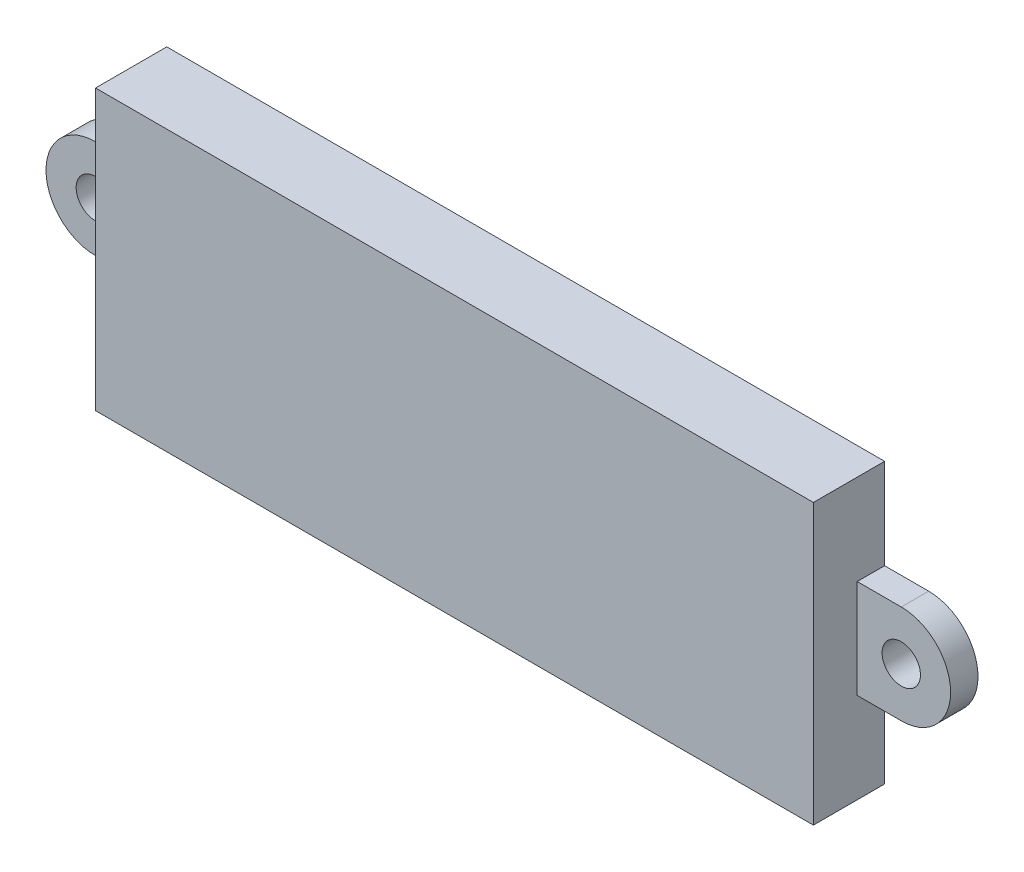
SolidWorks part; units mm, degrees
ref_plane "Спереди" through (0, 0, 0) normal (0, 0, 1) x (1, 0, 0)
ref_plane "Сверху" through (0, 0, 0) normal (0, 1, 0) x (1, 0, 0)
ref_plane "Справа" through (0, 0, 0) normal (1, 0, 0) x (0, 0, -1)
sketch "Эскиз1" plane through (0, 0, 0) normal (0, 0, 1) x (1, 0, 0)
  line L5 (0, 0) -> (123, 0)
  line L6 (0, 0) -> (0, 43)
  line L7 (0, 43) -> (123, 43)
  line L8 (123, 0) -> (123, 43)
  dimension "D1" = 123
  dimension "D2" = 43
extrude "Бобышка-Вытянуть1" add sketch "Эскиз1" along normal blind 4
sketch "Эскиз2" plane through (0, 0, 0) normal (0, 0, -1) x (-1, 0, 0)
  line L1 (-127, -4) -> (4, -4)
  line L2 (-127, -4) -> (-127, 47)
  line L3 (-127, 47) -> (4, 47)
  line L4 (4, -4) -> (4, 47)
  line L9 (-123, 0) -> (0, 0)
  line L10 (-123, 0) -> (-123, 43)
  line L11 (-123, 43) -> (0, 43)
  line L12 (0, 0) -> (0, 43)
  dimension "D1" = 4
  dimension "D2" = 4
  dimension "D3" = 4
  dimension "D4" = 4
extrude "Бобышка-Вытянуть2" add sketch "Эскиз2" along normal blind 9 and the other way blind 4
sketch "Эскиз3" plane through (0, 0, -9) normal (0, 0, -1) x (-1, 0, 0)
  line L0 (-127, 12.5) -> (-135.04, 12.5)
  line L1 (-127, 30.5) -> (-135.04, 30.5)
  line L2 (-134.7332, 21.5) -> (-138.54, 21.5) construction
  line L3 (-127, 30.5) -> (-127, 12.5)
  line L4 (-123, 21.5) -> (0, 21.5) construction
  line L5 (-123, 43) -> (-123, 0) construction
  line L6 (0, 0) -> (0, 43) construction
  line L7 (-127, 47) -> (-127, -4) construction
  arc A0 (-135.04, 12.5) -> (-135.04, 30.5) centre (-135.04, 21.5) cw
  circle A1 centre (-135.04, 21.5) radius 3.5
  dimension "D1" = 7
  dimension "D3" = 9
  dimension "D2" = 9
  dimension "D4" = 8.04
extrude "Бобышка-Вытянуть3" add sketch "Эскиз3" against normal blind 5
ref_plane "Плоскость1" through (61.5, 0, 0) normal (1, 0, 0) x (0, 0, -1)
mirror "Зеркальное отражение1" about plane through (61.5, 0, 0) normal (1, 0, 0) of "Бобышка-Вытянуть3"
